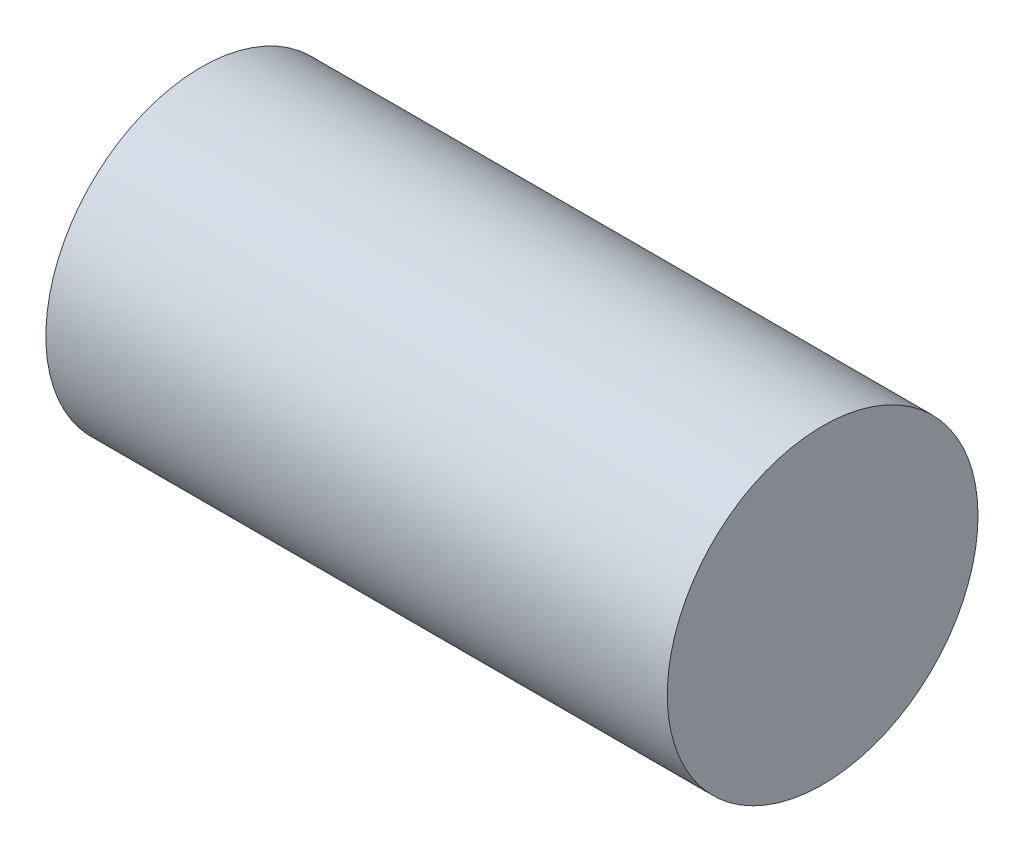
SolidWorks part; units mm, degrees
ref_plane "Front Plane" through (0, 0, 0) normal (0, 0, 1) x (1, 0, 0)
ref_plane "Top Plane" through (0, 0, 0) normal (0, 1, 0) x (1, 0, 0)
ref_plane "Right Plane" through (0, 0, 0) normal (1, 0, 0) x (0, 0, -1)
sketch "Sketch1" plane through (0, 0, 0) normal (1, 0, 0) x (0, 0, -1)
  circle A0 centre (0, 0) radius 5
extrude "Boss-Extrude1" add sketch "Sketch1" along normal blind 10 and the other way blind 10
